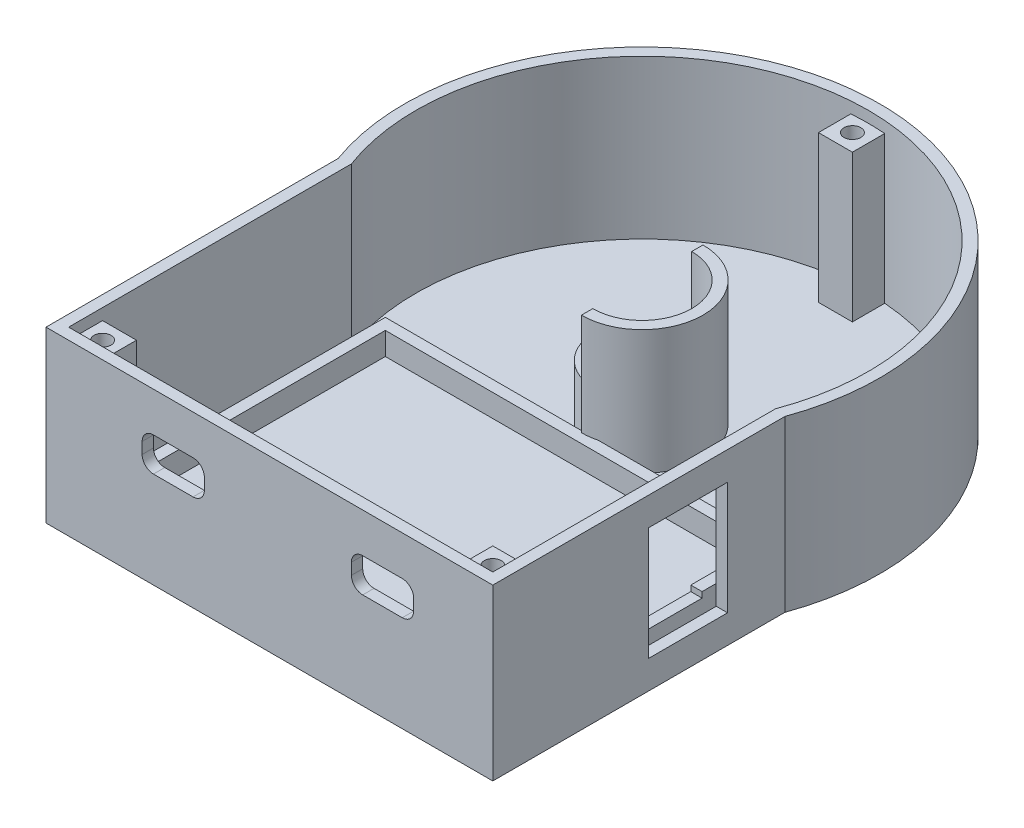
SolidWorks part; units mm, degrees
ref_plane "Front Plane" through (0, 0, 0) normal (0, 0, 1) x (1, 0, 0)
ref_plane "Top Plane" through (0, 0, 0) normal (0, 1, 0) x (1, 0, 0)
ref_plane "Right Plane" through (0, 0, 0) normal (1, 0, 0) x (0, 0, -1)
sketch "Sketch1" plane through (0, 0, 0) normal (0, 1, 0) x (1, 0, 0)
  line L2 (-37.5, 25) -> (-37.5, -25)
  line L3 (-37.5, -25) -> (37.5, -25)
  line L4 (37.5, 25) -> (37.5, -25)
  arc A0 (37.5, 25) -> (-37.5, 25) centre (0, 38.9194) ccw
  point P4 (0, -25)
  point P6 (37.5, 0)
  dimension "D4" = 40
  dimension "D1" = 75
  dimension "D2" = 50
  dimension "D3" = 50
extrude "Boss-Extrude1" add sketch "Sketch1" along normal blind 2
sketch "Sketch2" plane through (0, 0, 0) normal (0, -1, 0) x (1, 0, 0)
  line L2 (-37.5, -25) -> (-37.5, 25)
  line L3 (-37.5, 25) -> (37.5, 25)
  line L4 (37.5, -25) -> (37.5, 25)
  line L6 (-39.5, -24.6453) -> (-39.5, 27)
  line L7 (-39.5, 27) -> (39.5, 27)
  line L8 (39.5, -24.6453) -> (39.5, 27)
  arc A0 (-37.5, -25) -> (37.5, -25) centre (0, -38.9194) ccw
  arc A1 (-39.5, -24.6453) -> (39.5, -24.6453) centre (0, -38.9194) ccw
  dimension "D1" = 2
  dimension "D2" = 2
  dimension "D3" = 2
  dimension "D4" = 2
extrude "Boss-Extrude2" add sketch "Sketch2" against normal blind 30
sketch "Sketch3" plane through (0, 2, 0) normal (0, 1, 0) x (1, 0, 0)
  line L2 (0, 49.6694) -> (0, 47.6694)
  line L3 (0, 30.1694) -> (0, 28.1694)
  arc A3 (0, 30.1694) -> (0, 47.6694) centre (0, 38.9194) ccw
  arc A4 (0, 28.1694) -> (0, 49.6694) centre (0, 38.9194) ccw
  dimension "D1" = 17.5
  dimension "D2" = 2
extrude "Boss-Extrude3" add sketch "Sketch3" along normal blind 22
sketch "Sketch4" plane through (0, 2, 0) normal (0, 1, 0) x (1, 0, 0)
  circle A0 centre (0, 38.9194) radius 8.495
extrude "Boss-Extrude4" add sketch "Sketch4" along normal blind 9.7
sketch "Sketch5" plane through (0, 2, 0) normal (0, 1, 0) x (1, 0, 0)
  line L1 (-37.5, -25) -> (-31.5, -25)
  line L2 (-37.5, -25) -> (-37.5, -19)
  line L3 (-37.5, -19) -> (-31.5, -19)
  line L4 (-31.5, -25) -> (-31.5, -19)
  line L5 (37.5, -25) -> (31.5, -25)
  line L6 (37.5, -25) -> (37.5, -19)
  line L7 (37.5, -19) -> (31.5, -19)
  line L8 (31.5, -25) -> (31.5, -19)
  line L11 (-3, 79.087) -> (3, 79.087)
  line L12 (-3, 79.087) -> (-3, 73.087)
  line L13 (-3, 73.087) -> (3, 73.087)
  line L14 (3, 79.087) -> (3, 73.087)
  circle A4 centre (-34.5, -22) radius 1.5
  circle A5 centre (34.5, -22) radius 1.5
  circle A6 centre (0, 76.087) radius 1.5
  point P15 (0, 73.087)
  dimension "D1" = 6
  dimension "D2" = 6
  dimension "D6" = 3
  dimension "D7" = 3
  dimension "D8" = 6
  dimension "D9" = 3
  dimension "D3" = 6
  dimension "D4" = 6
  dimension "D5" = 6
extrude "Boss-Extrude5" add sketch "Sketch5" along normal blind 26
sketch "Sketch6" plane through (0, 0, 19) normal (0, 0, -1) x (-1, 0, 0)
  line L0 (-37.5, 28) -> (-37.5, 2) construction
  line L1 (37.5, 2) -> (-37.5, 2)
  line L2 (37.5, 2) -> (37.5, 22)
  line L3 (37.5, 22) -> (-37.5, 22)
  line L4 (-37.5, 2) -> (-37.5, 22)
  line L5 (37.5, 28) -> (37.5, 2) construction
  line L6 (31.5, 2) -> (-31.5, 2) construction
  dimension "D1" = 20
extrude "Cut-Extrude1" cut sketch "Sketch6" against normal up to surface (6 mm away) up to face at (0, 22, 25)
sketch "Sketch8" plane through (0, 2, 0) normal (0, 1, 0) x (1, 0, 0)
  line L0 (-39.5, -27) -> (39.5, -27) construction
  line L1 (-35, 28.5) -> (35, 28.5)
  line L2 (-35, 28.5) -> (-35, -21.5)
  line L3 (-35, -21.5) -> (35, -21.5)
  line L4 (35, 28.5) -> (35, -21.5)
  line L5 (37.5, -25) -> (-37.5, -25) construction
  line L6 (-33, 26.5) -> (33, 26.5)
  line L7 (-33, 26.5) -> (-33, -19.5)
  line L8 (-33, -19.5) -> (33, -19.5)
  line L9 (33, 26.5) -> (33, -19.5)
  point P4 (0, -27)
  point P9 (0, -21.5)
  dimension "D1" = 70
  dimension "D2" = 50
  dimension "D3" = 2
  dimension "D4" = 2
  dimension "D5" = 2
  dimension "D6" = 2
  dimension "D7" = 3.5
extrude "Boss-Extrude6" add sketch "Sketch8" along normal blind 4
sketch "Sketch9" plane through (0, 0, 27) normal (0, 0, 1) x (1, 0, 0)
  line L0 (-22.5, 20) -> (-11.5, 20) construction
  line L1 (-22.5, 23) -> (-11.5, 23)
  line L2 (-22.5, 23) -> (-22.5, 17)
  line L3 (-22.5, 17) -> (-11.5, 17)
  line L4 (-11.5, 23) -> (-11.5, 17)
  line L5 (14.5, 23) -> (25.5, 23)
  line L6 (14.5, 23) -> (14.5, 17)
  line L7 (14.5, 17) -> (25.5, 17)
  line L8 (25.5, 23) -> (25.5, 17)
  line L9 (-17, 23) -> (-17, 17) construction
  line L10 (-35, 6) -> (35, 6) construction
  line L11 (-35, 6) -> (-35, 2) construction
  point P14 (20, 23)
  dimension "D1" = 11
  dimension "D2" = 6
  dimension "D3" = 11
  dimension "D4" = 6
  dimension "D5" = 14
  dimension "D6" = 11
  dimension "D7" = 37
  dimension "D8" = 18
extrude "Cut-Extrude3" cut sketch "Sketch9" against normal blind 4
fillet "Fillet1" radius 2 8 edges at (25.5, 23, 26) (14.5, 23, 26) (14.5, 17, 26) (25.5, 17, 26) (-11.5, 17, 26) (-22.5, 17, 26) (-11.5, 23, 26) (-22.5, 23, 26)
sketch "Sketch10" plane through (39.5, 0, 0) normal (1, 0, 0) x (0, 0, -1)
  line L0 (-27, 15) -> (80.9194, 15) construction
  line L1 (0.5094, 25) -> (14.5094, 25)
  line L2 (0.5094, 25) -> (0.5094, 5)
  line L3 (0.5094, 5) -> (14.5094, 5)
  line L4 (14.5094, 25) -> (14.5094, 5)
  line L5 (-27, 30) -> (-27, 0) construction
  line L6 (80.9194, 0) -> (80.9194, 30) construction
  point P10 (0.5094, 15)
  dimension "D1" = 20
  dimension "D2" = 14
extrude "Cut-Extrude4" cut sketch "Sketch10" against normal blind 10
